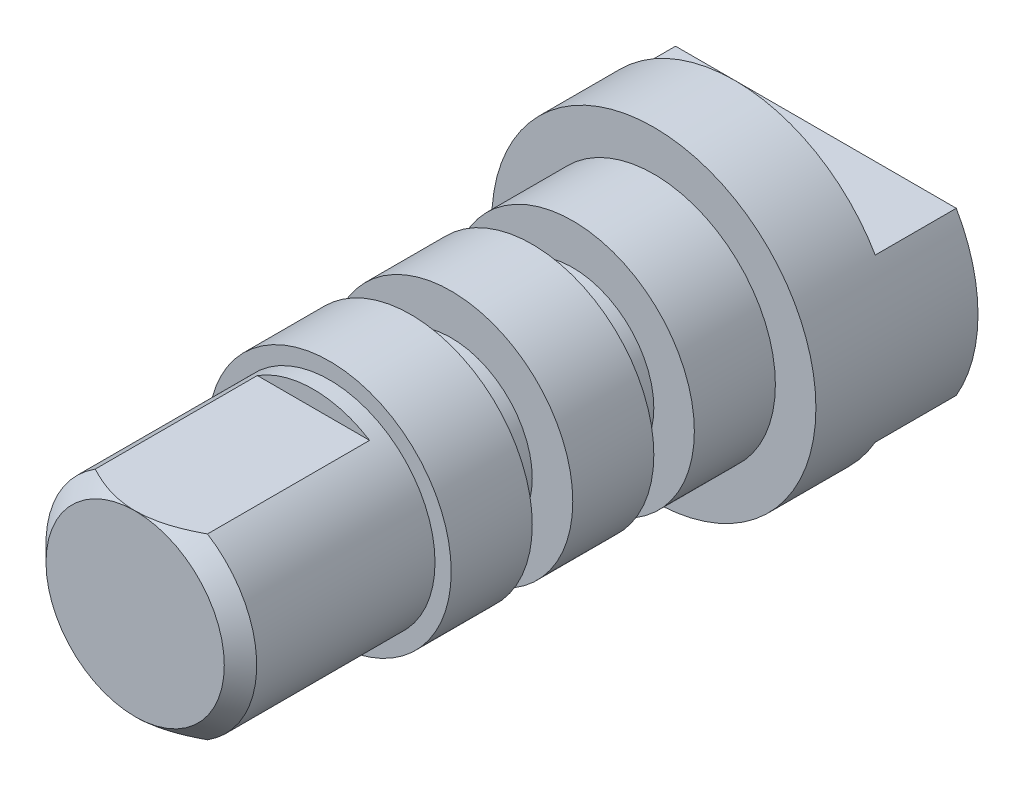
SolidWorks part; units mm, degrees
ref_plane "Przednia" through (0, 0, 0) normal (0, 0, 1) x (1, 0, 0)
ref_plane "Górna" through (0, 0, 0) normal (0, 1, 0) x (1, 0, 0)
ref_plane "Prawa" through (0, 0, 0) normal (1, 0, 0) x (0, 0, -1)
sketch "Szkic2" plane through (0, 0, 0) normal (0, 0, 1) x (1, 0, 0)
  circle A0 centre (0, 0) radius 10
  dimension "D1" = 20
extrude "Dodanie-wyciągnięcie1" add sketch "Szkic2" along normal blind 5
sketch "Szkic3" plane through (0, 0, 5) normal (0, 0, 1) x (1, 0, 0)
  circle A0 centre (0, 0) radius 7.5
  dimension "D1" = 15
extrude "Dodanie-wyciągnięcie2" add sketch "Szkic3" along normal blind 5
sketch "Szkic4" plane through (0, 0, 10) normal (0, 0, 1) x (1, 0, 0)
  circle A0 centre (0, 0) radius 5
  dimension "D1" = 10
extrude "Dodanie-wyciągnięcie3" add sketch "Szkic4" along normal blind 2.5
sketch "Szkic5" plane through (0, 0, 12.5) normal (0, 0, 1) x (1, 0, 0)
  circle A0 centre (0, 0) radius 7.5
extrude "Dodanie-wyciągnięcie4" add sketch "Szkic5" along normal blind 5
sketch "Szkic6" plane through (0, 0, 17.5) normal (0, 0, 1) x (1, 0, 0)
  circle A0 centre (0, 0) radius 5
  dimension "D1" = 10
extrude "Dodanie-wyciągnięcie5" add sketch "Szkic6" along normal blind 2.5
sketch "Szkic7" plane through (0, 0, 20) normal (0, 0, 1) x (1, 0, 0)
  circle A0 centre (0, 0) radius 7.5
extrude "Dodanie-wyciągnięcie6" add sketch "Szkic7" along normal blind 5
sketch "Szkic8" plane through (0, 0, 25) normal (0, 0, 1) x (1, 0, 0)
  circle A0 centre (0, 0) radius 6.5
  dimension "D1" = 13
extrude "Dodanie-wyciągnięcie7" add sketch "Szkic8" along normal blind 12
sketch "Szkic10" plane through (0, 0, 37) normal (0, 0, 1) x (1, 0, 0)
  line L1 (-4, 7.5) -> (4, 7.5)
  line L2 (-4, 7.5) -> (-4, 5.5)
  line L3 (-4, 5.5) -> (4, 5.5)
  line L4 (4, 7.5) -> (4, 5.5)
  line L5 (-4, 7.5) -> (4, 5.5) construction
  line L6 (-4, 5.5) -> (4, 7.5) construction
  line L7 (-4, -7.5) -> (4, -7.5)
  line L8 (-4, -7.5) -> (-4, -5.5)
  line L9 (-4, -5.5) -> (4, -5.5)
  line L10 (4, -7.5) -> (4, -5.5)
  line L11 (-4, -7.5) -> (4, -5.5) construction
  line L12 (-4, -5.5) -> (4, -7.5) construction
  circle A0 centre (0, 0) radius 6.5 construction
  circle A1 centre (0, 0) radius 6.5 construction
  point P0 (0, 6.5)
  point P9 (0, -6.5)
  dimension "D1" = 2
  dimension "D2" = 2
  dimension "D3" = 8
  dimension "D4" = 8
extrude "Wytnij-wyciągnięcie1" cut sketch "Szkic10" against normal blind 11
sketch "Szkic11" plane through (0, 0, 0) normal (0, 0, -1) x (-1, 0, 0)
  circle A0 centre (0, 0) radius 10
  dimension "D1" = 20
extrude "Dodanie-wyciągnięcie8" add sketch "Szkic11" along normal blind 5
sketch "Szkic13" plane through (0, 0, -5) normal (0, 0, -1) x (-1, 0, 0)
  line L2 (-8.6603, -5) -> (8.6603, -5)
  line L4 (-8.6603, 5) -> (8.6603, 5)
  line L6 (-8.6603, -5) -> (8.6603, 5) construction
  line L7 (-8.6603, 5) -> (8.6603, -5) construction
  circle A0 centre (0, 0) radius 10 construction
  arc A2 (-8.6603, -5) -> (8.6603, -5) centre (0, 0) ccw
  arc A4 (-8.6603, 5) -> (8.6603, 5) centre (0, 0) cw
  point P5 (0, 0)
  dimension "D1" = 10
extrude "Wytnij-wyciągnięcie2" cut sketch "Szkic13" against normal blind 5
chamfer "Sfazowanie1" distance 1 angle 45 2 edges at (-6.5, 0, 37) (6.5, 0, 37)
